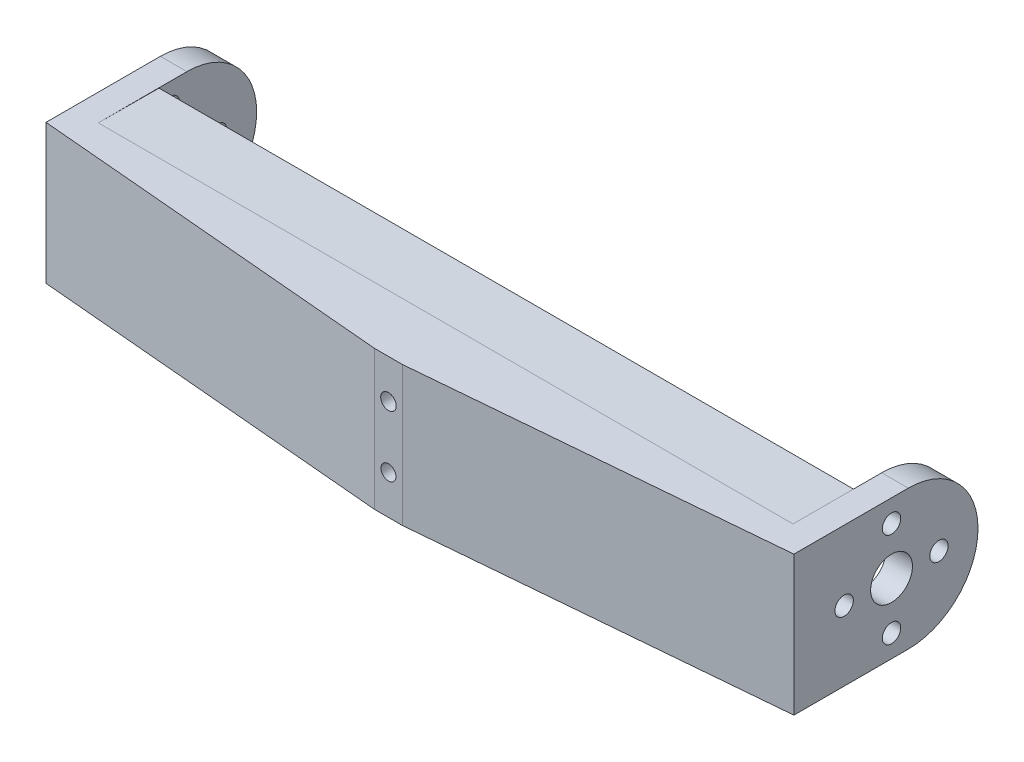
SolidWorks part; units mm, degrees
ref_plane "Plano frontal" through (0, 0, 0) normal (0, 0, 1) x (1, 0, 0)
ref_plane "Plano superior" through (0, 0, 0) normal (0, 1, 0) x (1, 0, 0)
ref_plane "Plano direito" through (0, 0, 0) normal (1, 0, 0) x (0, 0, -1)
sketch "Esboço1" plane through (0, 0, 0) normal (0, 1, 0) x (1, 0, 0)
  line L0 (-59.7157, 31.3398) -> (-59.7157, -1.6602)
  line L1 (-59.7157, 31.3398) -> (-54.9517, 31.3398)
  line L2 (-54.9517, 31.3398) -> (-54.9517, 2.9421)
  line L3 (-54.9517, 2.9421) -> (4.82, -2.2872)
  line L4 (4.82, -2.2872) -> (9.82, -2.2872)
  line L6 (-59.7157, -1.6602) -> (4.82, -7.3063)
  line L7 (4.82, -7.3063) -> (9.82, -7.3063)
  line L9 (74.3556, -1.6602) -> (9.82, -7.3063)
  line L10 (69.5916, 2.9421) -> (9.82, -2.2872)
  line L11 (69.5916, 31.3398) -> (69.5916, 2.9421)
  line L12 (74.3556, 31.3398) -> (69.5916, 31.3398)
  line L13 (74.3556, 31.3398) -> (74.3556, -1.6602)
  dimension "D1" = 95
  dimension "D2" = 95
  dimension "D3" = 5
extrude "Ressalto-extrusão1" add sketch "Esboço1" along normal blind 25
sketch "Esboço2" plane through (74.3556, 0, 0) normal (1, 0, 0) x (0, 0, -1)
  line L0 (31.3398, 25) -> (31.3398, 0) construction
  line L1 (-1.6602, 25) -> (31.3398, 25) construction
  line L2 (-1.6602, 0) -> (31.3398, 0) construction
  circle A0 centre (15.8398, 12.5) radius 3.75
  circle A1 centre (24.3398, 12.5) radius 1.65
  circle A2 centre (15.8398, 4) radius 1.65
  circle A3 centre (15.8398, 21) radius 1.65
  circle A4 centre (7.3398, 12.5) radius 1.65
  point P12 (31.3398, 12.5)
  dimension "D1" = 7
  dimension "D2" = 17
  dimension "D3" = 8.5
  dimension "D4" = 8.5
  dimension "D5" = 12.5
  dimension "D6" = 12.5
  dimension "D7" = 12.5
  dimension "D8" = 8.5
  dimension "D9" = 8.5
  dimension "D10" = 4
  dimension "D11" = 4
extrude "Corte-extrusão1" cut sketch "Esboço2" against normal through all
sketch "Esboço3" plane through (0, 0, 7.3063) normal (0, 0, 1) x (1, 0, 0)
  line L0 (4.82, 25) -> (9.82, 25) construction
  line L1 (4.82, 0) -> (9.82, 0) construction
  line L2 (4.82, 25) -> (4.82, 0) construction
  circle A0 centre (7.32, 7) radius 1.3408
  circle A1 centre (7.32, 18) radius 1.3954
  point P6 (7.32, 25)
  point P9 (7.32, 0)
  dimension "D1" = 7
  dimension "D2" = 7
  dimension "D3" = 2.5
  dimension "D4" = 2.5
fillet "Filete1" radius 12.5 4 edges at (-57.3337, 25, -31.3398) (-57.3337, 0, -31.3398) (71.9736, 25, -31.3398) (71.9736, 0, -31.3398)
sketch "Esboço6" plane through (69.5916, 0, 0) normal (-1, 0, 0) x (0, 0, 1)
  line L0 (-15.8398, 12.5) -> (-13.8398, 12.5)
  line L1 (-13.8398, 0.0597) -> (-2.9421, 0)
  line L2 (-13.8398, 24.9403) -> (-2.9421, 25)
  line L3 (-2.9421, 0) -> (-2.9421, 25)
  arc A0 (-13.8398, 0.0597) -> (-13.8398, 24.9403) centre (-15.8398, 12.5) ccw
  line M11 (-2.9421, 0) -> (-2.9421, 25)
extrude "Ressalto-extrusão2" add sketch "Esboço6" along normal up to surface (124.5434 mm away) contours A0 L1 L2 M11 region at (69.5916, 12.5, -2.9671) up to face at (-54.9517, 12.5, -5.6898)
sketch "Esboço8" plane through (0, 0, 0) normal (0, -1, 0) x (-1, 0, 0)
  line L0 (54.9517, 2.9421) -> (-4.82, -2.2872)
  line L4 (-9.82, -2.2872) -> (-69.5916, 2.9421)
  line L6 (-4.82, -2.2872) -> (-9.82, -2.2872)
  line L7 (-69.5916, 2.9421) -> (54.9517, 2.9421)
extrude "Ressalto-extrusão3" add sketch "Esboço8" against normal blind 25
extrude "Corte-extrusão4" cut sketch "Esboço3" against normal blind 25
ref_plane "Plano1" through (0, 0, -5.9437) normal (0, 0, 1) x (1, 0, 0)
sketch "Esboço10" plane through (0, 0, -5.9437) normal (0, 0, 1) x (1, 0, 0)
  circle A0 centre (7.32, 7) radius 1.55
  circle A1 centre (7.32, 18) radius 1.55
extrude "Corte-extrusão5" cut sketch "Esboço10" along normal blind 3
